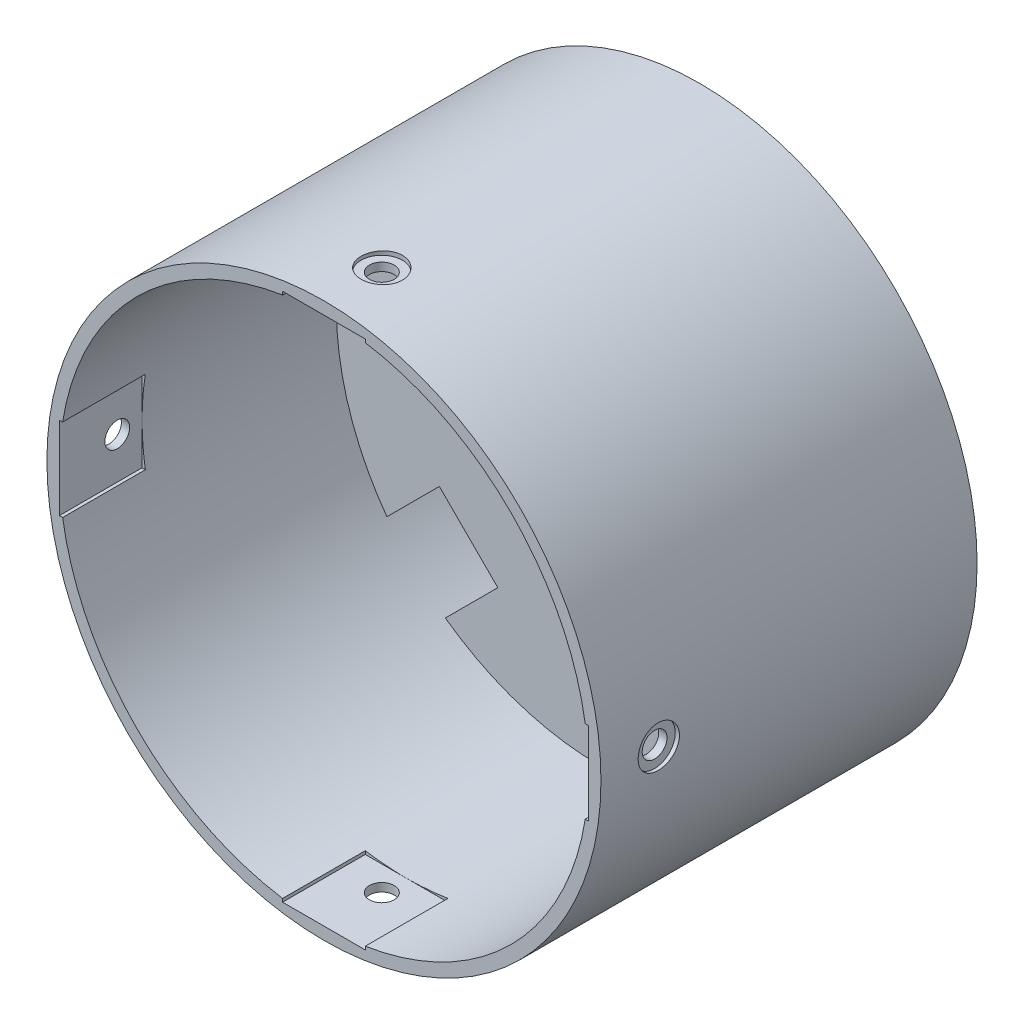
SolidWorks part; units mm, degrees
ref_plane "Front Plane" through (0, 0, 0) normal (0, 0, 1) x (1, 0, 0)
ref_plane "Top Plane" through (0, 0, 0) normal (0, 1, 0) x (1, 0, 0)
ref_plane "Right Plane" through (0, 0, 0) normal (1, 0, 0) x (0, 0, -1)
sketch "Sketch1" plane through (0, 0, 0) normal (0, 0, 1) x (1, 0, 0)
  circle A0 centre (0, 0) radius 31.51
  circle A1 centre (0, 0) radius 33.51
  circle A2 centre (0, 0) radius 31.8
  dimension "D1" = 63.02
  dimension "D2" = 2
extrude "Boss-Extrude1" add sketch "Sketch1" along normal blind 2 contours A1
sketch "Sketch2" plane through (0, 0, 2) normal (0, 0, 1) x (1, 0, 0)
  circle A0 centre (0, 0) radius 32
  circle A1 centre (0, 0) radius 33.51
  dimension "D1" = 64
extrude "Boss-Extrude2" add sketch "Sketch2" along normal blind 23.5
sketch "Sketch3" plane through (0, 0, 0) normal (0, 0, -1) x (-1, 0, 0)
  line L0 (0, 0) -> (33.51, 0) construction
  circle A0 centre (0, 0) radius 33.51 construction
  circle A1 centre (21.85, 0) radius 1.5
  circle A2 centre (13.01, 0) radius 1.5
  circle A3 centre (0, -21.85) radius 1.5
  circle A4 centre (0, -13.01) radius 1.5
  circle A5 centre (-21.85, 0) radius 1.5
  circle A6 centre (-13.01, 0) radius 1.5
  circle A7 centre (0, 21.85) radius 1.5
  circle A8 centre (0, 13.01) radius 1.5
  point P25 (0, 0)
  dimension "D1" = 3
  dimension "D2" = 3
  dimension "D3" = 21.85
  dimension "D4" = 13.01
  dimension "D5" = 4
extrude "Cut-Extrude1" cut sketch "Sketch3" against normal through all
sketch "Sketch4" plane through (0, 0, 2) normal (0, 0, 1) x (1, 0, 0)
  circle A0 centre (0, 0) radius 10
  dimension "D1" = 20
extrude "Cut-Extrude2" cut sketch "Sketch4" against normal through all
sketch "Sketch5" plane through (0, 0, 2) normal (0, 0, 1) x (1, 0, 0)
  line L0 (0, 0) -> (32, 0)
  line L2 (0, 32) -> (0, 0)
  line L3 (12.4645, 19.5355) -> (19.5355, 12.4645)
  line L4 (19.5355, -12.4645) -> (12.4645, -19.5355)
  line L5 (12.4645, -19.5355) -> (18.814, -25.885)
  line L6 (19.5355, 12.4645) -> (25.885, 18.814)
  line L7 (19.5355, -12.4645) -> (25.885, -18.814)
  line L8 (12.4645, 19.5355) -> (18.814, 25.885)
  line L9 (-12.4645, -19.5355) -> (-19.5355, -12.4645)
  line L10 (-19.5355, -12.4645) -> (-25.885, -18.814)
  line L11 (-12.4645, -19.5355) -> (-18.814, -25.885)
  line L12 (-19.5355, 12.4645) -> (-12.4645, 19.5355)
  line L13 (-12.4645, 19.5355) -> (-18.814, 25.885)
  line L14 (-19.5355, 12.4645) -> (-25.885, 18.814)
  circle A0 centre (0, 0) radius 32 construction
  circle A1 centre (0, 0) radius 32 construction
  arc A2 (25.885, 18.814) -> (18.7584, 25.9253) centre (0, 0) ccw
  arc A3 (18.814, -25.885) -> (25.9253, -18.7584) centre (0, 0) ccw
  arc A4 (-25.885, -18.814) -> (-18.7584, -25.9253) centre (0, 0) ccw
  arc A5 (-18.814, 25.885) -> (-25.9253, 18.7584) centre (0, 0) ccw
  point P32 (0, 0)
  circle M13 centre (0, 0) radius 32
  dimension "D1" = 4
extrude "Cut-Extrude3" cut sketch "Sketch5" against normal blind 10 and the other way through all contours L14 L12 L13 M13 | L8 L3 L6 M13 | L11 L9 L10 M13 | L7 L4 L5 M13 region at (19.268, 19.268, 2) region at (-19.268, 19.268, 2) region at (19.268, -19.268, 2) region at (-19.268, -19.268, 2)
sketch "Sketch6" plane through (0, 0, 0) normal (0, 0, -1) x (-1, 0, 0)
  circle A0 centre (0, 0) radius 33.51
  circle A1 centre (0, 0) radius 32
extrude "Boss-Extrude3" add sketch "Sketch6" along normal blind 10
fillet "Fillet1" radius 1 4 edges at (32, 0, 0) (0, -32, 0) (-32, 0, 0) (0, 32, 0)
sketch "Sketch7" plane through (0, 0, 25.5) normal (0, 0, 1) x (1, 0, 0)
  circle A0 centre (0, 0) radius 32
  circle A1 centre (0, 0) radius 33.51
extrude "Boss-Extrude4" add sketch "Sketch7" along normal blind 10
sketch "Sketch8" plane through (0, 0, 35.5) normal (0, 0, 1) x (1, 0, 0)
  line L0 (0, 0) -> (32, 0)
  line L1 (32, 0) -> (32, 5)
  line L2 (32, 5) -> (31.607, 5)
  line L3 (31.607, 5) -> (31.607, -5)
  line L4 (31.607, -5) -> (32, -5)
  line L5 (32, -5) -> (32, 0)
  line L6 (-5, -32) -> (0, -32)
  line L7 (5, -31.607) -> (-5, -31.607)
  line L8 (5, -32) -> (5, -31.607)
  line L9 (0, -32) -> (5, -32)
  line L10 (-5, -31.607) -> (-5, -32)
  line L11 (-32, 5) -> (-32, 0)
  line L12 (-31.607, -5) -> (-31.607, 5)
  line L13 (-32, -5) -> (-31.607, -5)
  line L14 (-32, 0) -> (-32, -5)
  line L15 (-31.607, 5) -> (-32, 5)
  line L16 (5, 32) -> (0, 32)
  line L17 (-5, 31.607) -> (5, 31.607)
  line L18 (-5, 32) -> (-5, 31.607)
  line L19 (0, 32) -> (-5, 32)
  line L20 (5, 31.607) -> (5, 32)
  arc A0 (25.885, -18.814) -> (25.885, 18.814) centre (0, 0) ccw construction
  point P28 (0, 0)
  dimension "D1" = 4
extrude "Cut-Extrude4" cut sketch "Sketch8" against normal blind 10 contours L12 L15 L11 L14 L13 | L17 L20 L16 L19 L18 | L1 L2 L3 L4 L5 | L7 L10 L6 L9 L8
sketch "Sketch9" plane through (0, 32, 0) normal (0, -1, 0) x (1, 0, 0)
  line L0 (0, 25.5) -> (0, 28.5) construction
  circle A0 centre (0, 28.5) radius 1.5
  dimension "D2" = 3
  dimension "D1" = 3
extrude "Cut-Extrude5" cut sketch "Sketch9" against normal blind 10
pattern_circular "CirPattern1" count 4 every 90 about axis through (0, 0, 25.5) along (0, 0, -1) of "Cut-Extrude5" reverse direction yes
ref_plane "Plane1" through (0, 34, 0) normal (0, -1, 0) x (-1, 0, 0)
sketch "Sketch11" plane through (0, 34, 0) normal (0, -1, 0) x (-1, 0, 0)
  circle A0 centre (0, -28.5) radius 2.5
  dimension "D1" = 5
extrude "Cut-Extrude6" cut sketch "Sketch11" along normal blind 1
pattern_circular "CirPattern2" count 4 every 90 about axis through (0, 0, 25.5) along (0, 0, -1) of "Cut-Extrude6"
